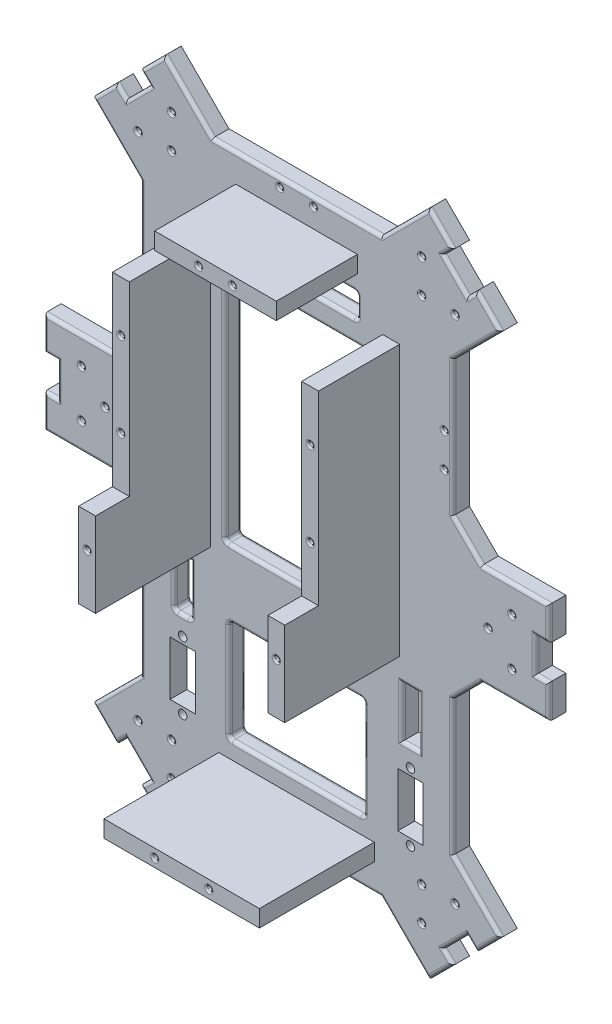
SolidWorks part; units mm, degrees
ref_plane "Płaszczyzna przednia" through (0, 0, 0) normal (0, 0, 1) x (1, 0, 0)
ref_plane "Płaszczyzna górna" through (0, 0, 0) normal (0, 1, 0) x (1, 0, 0)
ref_plane "Płaszczyzna prawa" through (0, 0, 0) normal (1, 0, 0) x (0, 0, -1)
sketch "Szkic1" plane through (0, 0, 0) normal (0, 0, 1) x (1, 0, 0)
  line L0 (0, 0) -> (-50, 0)
  line L1 (-50, 0) -> (-64.1421, 14.1421)
  line L2 (-64.1421, 14.1421) -> (-71.2132, 7.0711)
  line L3 (-71.2132, 7.0711) -> (-68.3848, 4.2426)
  line L4 (-68.3848, 4.2426) -> (-75.4558, -2.8284)
  line L5 (-75.4558, -2.8284) -> (-78.2843, 0)
  line L6 (-78.2843, 0) -> (-85.3553, -7.0711)
  line L7 (-85.3553, -7.0711) -> (-71.2132, -21.2132)
  line L8 (-71.2132, -21.2132) -> (-71.2132, -61.2132)
  line L9 (0, 0) -> (14.1421, 14.1421)
  line L10 (14.1421, 14.1421) -> (21.2132, 7.0711)
  line L11 (21.2132, 7.0711) -> (18.3848, 4.2426)
  line L12 (18.3848, 4.2426) -> (25.4558, -2.8284)
  line L13 (25.4558, -2.8284) -> (28.2843, 0)
  line L14 (28.2843, 0) -> (35.3553, -7.0711)
  line L15 (35.3553, -7.0711) -> (21.2132, -21.2132)
  line L16 (21.2132, -21.2132) -> (21.2132, -61.2132)
  line L17 (-71.2132, -61.2132) -> (-79.6985, -69.6985)
  line L18 (-79.6985, -69.6985) -> (-99.6985, -69.6985)
  line L19 (-99.6985, -69.6985) -> (-99.6985, -79.6985)
  line L20 (-99.6985, -79.6985) -> (-95.6985, -79.6985)
  line L21 (-95.6985, -79.6985) -> (-95.6985, -89.6985)
  line L22 (-95.6985, -89.6985) -> (-99.6985, -89.6985)
  line L23 (-99.6985, -89.6985) -> (-99.6985, -99.6985)
  line L24 (-99.6985, -99.6985) -> (-79.6985, -99.6985)
  line L25 (21.2132, -61.2132) -> (29.6985, -69.6985)
  line L26 (29.6985, -69.6985) -> (49.6985, -69.6985)
  line L27 (49.6985, -69.6985) -> (49.6985, -79.6985)
  line L28 (49.6985, -79.6985) -> (45.6985, -79.6985)
  line L29 (45.6985, -79.6985) -> (45.6985, -89.6985)
  line L30 (45.6985, -89.6985) -> (49.6985, -89.6985)
  line L31 (49.6985, -89.6985) -> (49.6985, -99.6985)
  line L32 (49.6985, -99.6985) -> (29.6985, -99.6985)
  line L33 (29.6985, -99.6985) -> (21.2132, -108.1838)
  line L34 (-79.6985, -99.6985) -> (-71.2132, -108.1838)
  line L35 (-71.2132, -108.1838) -> (-71.2132, -148.1838)
  line L36 (21.2132, -108.1838) -> (21.2132, -148.1838)
  line L37 (-71.2132, -148.1838) -> (-85.3553, -162.3259)
  line L38 (-85.3553, -162.3259) -> (-78.2843, -169.397)
  line L39 (-78.2843, -169.397) -> (-75.4558, -166.5685)
  line L40 (-75.4558, -166.5685) -> (-68.3848, -173.6396)
  line L41 (-68.3848, -173.6396) -> (-71.2132, -176.468)
  line L42 (-71.2132, -176.468) -> (-64.1421, -183.5391)
  line L43 (-64.1421, -183.5391) -> (-50, -169.397)
  line L44 (21.2132, -148.1838) -> (35.3553, -162.3259)
  line L45 (35.3553, -162.3259) -> (28.2843, -169.397)
  line L46 (28.2843, -169.397) -> (25.4558, -166.5685)
  line L47 (25.4558, -166.5685) -> (18.3848, -173.6396)
  line L48 (18.3848, -173.6396) -> (21.2132, -176.468)
  line L49 (21.2132, -176.468) -> (14.1421, -183.5391)
  line L50 (14.1421, -183.5391) -> (0, -169.397)
  line L51 (-50, -169.397) -> (0, -169.397)
  dimension "D1" = 225
  dimension "D2" = 225
  dimension "D3" = 20
  dimension "D4" = 20
  dimension "D5" = 10
  dimension "D6" = 4
  dimension "D7" = 50
  dimension "D8" = 10
  dimension "D9" = 10
  dimension "D10" = 20
  dimension "D11" = 4
  dimension "D12" = 10
  dimension "D13" = 4
  dimension "D14" = 10
  dimension "D15" = 4
  dimension "D16" = 10
  dimension "D17" = 20
  dimension "D18" = 225
  dimension "D19" = 40
  dimension "D20" = 12
  dimension "D21" = 20
  dimension "D22" = 10
  dimension "D23" = 4
  dimension "D24" = 10
  dimension "D25" = 4
  dimension "D26" = 10
  dimension "D27" = 20
  dimension "D29" = 12
  dimension "D30" = 20
  dimension "D31" = 10
  dimension "D32" = 4
  dimension "D33" = 10
  dimension "D34" = 4
  dimension "D35" = 10
  dimension "D36" = 20
  dimension "D37" = 12
  dimension "D38" = 12
  dimension "D39" = 40
  dimension "D40" = 40
  dimension "D41" = 20
  dimension "D42" = 10
  dimension "D43" = 4
  dimension "D44" = 10
  dimension "D45" = 4
  dimension "D46" = 10
  dimension "D47" = 20
  dimension "D48" = 20
  dimension "D49" = 10
  dimension "D50" = 4
  dimension "D51" = 10
  dimension "D52" = 4
  dimension "D53" = 10
  dimension "D54" = 20
  dimension "D55" = 135
  dimension "D56" = 90
  dimension "D57" = 270
  dimension "D58" = 225
  dimension "D59" = 225
  dimension "D60" = 135
extrude "Dodanie-wyciągnięcie1" add sketch "Szkic1" along normal blind 5 contours L36 L44 L45 L46 L47 L48 L49 L50 L51 L43 L42 L41 L40 L39 L38 L37 L35 L34 L24 L23 L22 L21 L20 L19 L18 L17 L8 L7 L6 L5 L4 L3 L2 L1 L0 L9 L10 L11 L12 L13 L14 L15 L16 L25 L26 L27 L28 L29 L30 L31 L32 L33
sketch "Szkic11" plane through (0, 0, 5) normal (0, 0, 1) x (1, 0, 0)
  line L0 (-79.6985, -69.6985) -> (-99.6985, -69.6985) construction
  line L1 (-85.3553, -7.0711) -> (-71.2132, -21.2132) construction
  line L2 (-99.6985, -69.6985) -> (-99.6985, -79.6985) construction
  line L3 (-99.6985, -99.6985) -> (-79.6985, -99.6985) construction
  line L4 (-78.2843, 0) -> (-85.3553, -7.0711) construction
  line L5 (-50, 0) -> (-64.1421, 14.1421) construction
  line L6 (-64.1421, 14.1421) -> (-71.2132, 7.0711) construction
  line L7 (14.1421, 14.1421) -> (21.2132, 7.0711) construction
  line L8 (35.3553, -7.0711) -> (21.2132, -21.2132) construction
  line L9 (28.2843, 0) -> (35.3553, -7.0711) construction
  line L10 (0, 0) -> (14.1421, 14.1421) construction
  line L11 (49.6985, -89.6985) -> (49.6985, -99.6985) construction
  line L12 (49.6985, -99.6985) -> (29.6985, -99.6985) construction
  line L13 (49.6985, -69.6985) -> (49.6985, -79.6985) construction
  line L14 (29.6985, -69.6985) -> (49.6985, -69.6985) construction
  line L15 (21.2132, -176.468) -> (14.1421, -183.5391) construction
  line L16 (14.1421, -183.5391) -> (0, -169.397) construction
  line L17 (35.3553, -162.3259) -> (28.2843, -169.397) construction
  line L18 (21.2132, -148.1838) -> (35.3553, -162.3259) construction
  line L19 (-85.3553, -162.3259) -> (-78.2843, -169.397) construction
  line L20 (-71.2132, -176.468) -> (-64.1421, -183.5391) construction
  line L21 (-64.1421, -183.5391) -> (-50, -169.397) construction
  line L22 (-71.2132, -148.1838) -> (-85.3553, -162.3259) construction
  line L23 (-99.6985, -89.6985) -> (-99.6985, -99.6985) construction
  circle A0 centre (-81.6985, -84.6985) radius 0.8
  circle A1 centre (-88.6985, -77.6985) radius 0.8
  circle A2 centre (-88.6985, -91.6985) radius 0.8
  circle A3 centre (-62.0208, -9.1924) radius 0.8
  circle A4 centre (-62.0208, 0.7071) radius 0.8
  circle A5 centre (-71.9203, -9.1924) radius 0.8
  circle A6 centre (12.0208, -9.1924) radius 0.8
  circle A7 centre (12.0208, 0.7071) radius 0.8
  circle A8 centre (21.9203, -9.1924) radius 0.8
  circle A9 centre (31.6985, -84.6985) radius 0.8
  circle A10 centre (38.6985, -77.6985) radius 0.8
  circle A11 centre (38.6985, -91.6985) radius 0.8
  circle A12 centre (12.0208, -160.2046) radius 0.8
  circle A13 centre (21.9203, -160.2046) radius 0.8
  circle A14 centre (12.0208, -170.1041) radius 0.8
  circle A15 centre (-62.0208, -160.2046) radius 0.8
  circle A16 centre (-71.9203, -160.2046) radius 0.8
  circle A17 centre (-62.0208, -170.1041) radius 0.8
  dimension "D1" = 1.6
  dimension "D4" = 1.6
  dimension "D5" = 1.6
  dimension "D10" = 1.6
  dimension "D11" = 1.6
  dimension "D12" = 1.6
  dimension "D19" = 1.6
  dimension "D20" = 1.6
  dimension "D21" = 1.6
  dimension "D30" = 1.6
  dimension "D31" = 1.6
  dimension "D32" = 1.6
  dimension "D41" = 1.6
  dimension "D42" = 1.6
  dimension "D43" = 1.6
  dimension "D50" = 1.6
  dimension "D51" = 1.6
  dimension "D52" = 1.6
  dimension "D2" = 15
  dimension "D3" = 18
  dimension "D6" = 7
  dimension "D7" = 7
  dimension "D8" = 8
  dimension "D9" = 8
  dimension "D13" = 18
  dimension "D14" = 15
  dimension "D15" = 8
  dimension "D16" = 8
  dimension "D17" = 11
  dimension "D18" = 11
  dimension "D22" = 18
  dimension "D23" = 15
  dimension "D24" = 11
  dimension "D25" = 11
  dimension "D26" = 8
  dimension "D27" = 8
  dimension "D28" = 14
  dimension "D29" = 14
  dimension "D33" = 18
  dimension "D34" = 15
  dimension "D35" = 11
  dimension "D36" = 11
  dimension "D37" = 8
  dimension "D38" = 8
  dimension "D39" = 14
  dimension "D40" = 7
  dimension "D44" = 18
  dimension "D45" = 15
  dimension "D46" = 11
  dimension "D47" = 11
  dimension "D48" = 8
  dimension "D49" = 8
  dimension "D53" = 18
  dimension "D54" = 11
  dimension "D55" = 11
  dimension "D56" = 8
  dimension "D57" = 15
  dimension "D58" = 8
  dimension "D59" = 14
  dimension "D60" = 14
  dimension "D61" = 14
  dimension "D62" = 11
  dimension "D63" = 11
extrude "Wytnij-wyciągnięcie7" cut sketch "Szkic11" against normal blind 60 and the other way blind 42
sketch "Szkic12" plane through (0, 0, 5) normal (0, 0, 1) x (1, 0, 0)
  line L0 (0, 0) -> (-50, 0) construction
  line L1 (-71.2132, -21.2132) -> (-71.2132, -61.2132) construction
  line L2 (-50, -169.397) -> (0, -169.397) construction
  line L3 (21.2132, -21.2132) -> (21.2132, -61.2132) construction
  circle A0 centre (-30, -2.5) radius 0.75
  circle A1 centre (-20, -2.5) radius 0.75
  circle A2 centre (-30, -166.897) radius 0.75
  circle A3 centre (-20, -166.897) radius 0.75
  circle A4 centre (-68.7132, -40.5) radius 0.75
  circle A5 centre (-68.7132, -50.5) radius 0.75
  circle A6 centre (18.7132, -40.5) radius 0.75
  circle A7 centre (18.7132, -50.5) radius 0.75
  dimension "D2" = 1.5
  dimension "D3" = 1.5
  dimension "D8" = 1.5
  dimension "D9" = 1.5
  dimension "D15" = 1.5
  dimension "D16" = 1.5
  dimension "D17" = 1.5
  dimension "D18" = 1.5
  dimension "D1" = 2.5
  dimension "D4" = 2.5
  dimension "D5" = 20
  dimension "D6" = 10
  dimension "D7" = 20
  dimension "D10" = 2.5
  dimension "D11" = 2.5
  dimension "D12" = 20
  dimension "D13" = 10
  dimension "D14" = 20
  dimension "D19" = 2.5
  dimension "D20" = 2.5
  dimension "D21" = 2.5
  dimension "D22" = 2.5
  dimension "D23" = 40.5
  dimension "D24" = 50.5
  dimension "D25" = 40.5
  dimension "D26" = 50.5
extrude "Wytnij-wyciągnięcie8" cut sketch "Szkic12" against normal blind 66 and the other way blind 36
sketch "Szkic13" plane through (0, 0, 0) normal (0, 0, 1) x (1, 0, 0)
  line L0 (0, 0) -> (-50, 0) construction
  line L1 (-46.2132, -31.5) -> (-3.7868, -31.5)
  line L2 (-46.2132, -31.5) -> (-46.2132, -101.5)
  line L3 (-46.2132, -101.5) -> (-3.7868, -101.5)
  line L4 (-3.7868, -31.5) -> (-3.7868, -101.5)
  line L9 (-71.2132, -21.2132) -> (-71.2132, -61.2132) construction
  line L10 (21.2132, -21.2132) -> (21.2132, -61.2132) construction
  line L11 (-71.2132, -108.1838) -> (-71.2132, -148.1838) construction
  line L12 (-45.0032, -121.397) -> (-5.0032, -121.397)
  line L13 (-45.0032, -121.397) -> (-45.0032, -151.397)
  line L14 (-45.0032, -151.397) -> (-5.0032, -151.397)
  line L15 (-5.0032, -121.397) -> (-5.0032, -151.397)
  line L16 (21.2132, -108.1838) -> (21.2132, -148.1838) construction
  line L17 (-50, -169.397) -> (0, -169.397) construction
  line L19 (-61.2132, -111.5) -> (-56.2132, -111.5)
  line L20 (-61.2132, -111.5) -> (-61.2132, -126.5)
  line L21 (-61.2132, -126.5) -> (-56.2132, -126.5)
  line L22 (-56.2132, -111.5) -> (-56.2132, -126.5)
  line L23 (-62.4632, -134) -> (-54.9632, -134)
  line L24 (-62.4632, -134) -> (-62.4632, -150)
  line L25 (-62.4632, -150) -> (-54.9632, -150)
  line L26 (-54.9632, -134) -> (-54.9632, -150)
  line L31 (4.9632, -134) -> (12.4632, -134)
  line L32 (4.9632, -134) -> (4.9632, -150)
  line L33 (4.9632, -150) -> (12.4632, -150)
  line L34 (12.4632, -134) -> (12.4632, -150)
  line L35 (-43.0032, -18) -> (-7.0032, -18)
  line L36 (-43.0032, -18) -> (-43.0032, -25)
  line L37 (-43.0032, -25) -> (-7.0032, -25)
  line L38 (-7.0032, -18) -> (-7.0032, -25)
  line L39 (6.2132, -111.5) -> (11.2132, -111.5)
  line L40 (6.2132, -111.5) -> (6.2132, -126.5)
  line L41 (6.2132, -126.5) -> (11.2132, -126.5)
  line L42 (11.2132, -111.5) -> (11.2132, -126.5)
  circle A0 centre (8.7132, -132) radius 1.25
  circle A1 centre (8.7132, -152) radius 1.25
  circle A2 centre (-58.7132, -132) radius 1.25
  circle A3 centre (-58.7132, -152) radius 1.25
  dimension "D39" = 2.5
  dimension "D40" = 2.5
  dimension "D30" = 2.5
  dimension "D41" = 2.5
  dimension "D1" = 70
  dimension "D2" = 31.5
  dimension "D3" = 25
  dimension "D5" = 25
  dimension "D6" = 15
  dimension "D7" = 12.603
  dimension "D8" = 7.5
  dimension "D9" = 40
  dimension "D10" = 26.21
  dimension "D11" = 26.2164
  dimension "D12" = 30
  dimension "D13" = 18
  dimension "D14" = 2
  dimension "D15" = 10
  dimension "D16" = 5
  dimension "D17" = 10
  dimension "D18" = 15
  dimension "D19" = 8.75
  dimension "D20" = 7.5
  dimension "D21" = 7.5
  dimension "D22" = 16
  dimension "D23" = 0
  dimension "D24" = 7.5
  dimension "D25" = 5
  dimension "D26" = 3.75
  dimension "D27" = 3.75
  dimension "D28" = 8.75
  dimension "D29" = 16
  dimension "D31" = 9.9664
  dimension "D32" = 28.21
  dimension "D33" = 36
  dimension "D34" = 28.2164
  dimension "D35" = 7
  dimension "D36" = 18
  dimension "D37" = 3.75
  dimension "D38" = 3.75
  dimension "50" = 20
  dimension "D42" = 2
  dimension "D43" = 2
  dimension "D44" = 10
extrude "Wytnij-wyciągnięcie9" cut sketch "Szkic13" against normal blind 47 and the other way blind 54
sketch "Szkic14" plane through (0, 0, 5) normal (0, 0, 1) x (1, 0, 0)
  line L0 (-50.4982, -25) -> (-55.4982, -25)
  line L1 (-55.4982, -25) -> (-55.4982, -105)
  line L2 (-55.4982, -105) -> (-50.4982, -105)
  line L3 (-50.4982, -105) -> (-50.4982, -25)
  line L4 (5.5018, -25) -> (5.5018, -105)
  line L5 (5.5018, -105) -> (0.5018, -105)
  line L6 (0.5018, -25) -> (5.5018, -25)
  line L7 (0.5018, -105) -> (0.5018, -25)
  line L8 (-46.2132, -101.5) -> (-46.2132, -31.5) construction
  line L10 (-5.0032, -151.397) -> (-45.0032, -151.397) construction
  line L11 (0, 0) -> (-50, 0) construction
  line L12 (-3.7868, -31.5) -> (-3.7868, -101.5) construction
  line L13 (-48.0032, -156.397) -> (-2.0032, -156.397)
  line L14 (-2.0032, -156.397) -> (-2.0032, -161.397)
  line L15 (-2.0032, -161.397) -> (-48.0032, -161.397)
  line L16 (-48.0032, -161.397) -> (-48.0032, -156.397)
  line L18 (-71.2132, -108.1838) -> (-71.2132, -148.1838) construction
  line L19 (-43.0032, -13.197) -> (-7.0032, -13.197)
  line L20 (-7.0032, -13.197) -> (-7.0032, -8.197)
  line L21 (-7.0032, -8.197) -> (-43.0032, -8.197)
  line L22 (-43.0032, -8.197) -> (-43.0032, -13.197)
  line L24 (-71.2132, -21.2132) -> (-71.2132, -61.2132) construction
  circle A0 centre (-30.0032, -10.697) radius 0.75
  circle A1 centre (-20.0032, -10.697) radius 0.75
  circle A2 centre (-33.0032, -158.897) radius 0.75
  circle A3 centre (-17.0032, -158.897) radius 0.75
  circle A4 centre (-52.9982, -40) radius 0.75
  circle A5 centre (-52.9982, -65) radius 0.75
  circle A6 centre (-52.9982, -90) radius 0.75
  circle A7 centre (3.0018, -40) radius 0.75
  circle A8 centre (3.0018, -65) radius 0.75
  circle A9 centre (3.0018, -90) radius 0.75
  dimension "D21" = 1.5
  dimension "D22" = 1.5
  dimension "D26" = 1.5
  dimension "D27" = 1.5
  dimension "D33" = 1.5
  dimension "D34" = 1.5
  dimension "D35" = 1.5
  dimension "D42" = 1.5
  dimension "D43" = 1.5
  dimension "D44" = 1.5
  dimension "D1" = 80
  dimension "D2" = 5
  dimension "D3" = 5
  dimension "D4" = 80
  dimension "D5" = 51
  dimension "D6" = 4.285
  dimension "D7" = 4.2886
  dimension "D8" = 25
  dimension "D9" = 25
  dimension "D10" = 5
  dimension "D11" = 5
  dimension "D12" = 46
  dimension "D13" = 23.21
  dimension "D14" = 143.2
  dimension "D15" = 5
  dimension "D16" = 28.21
  dimension "D17" = 36
  dimension "D18" = 2.5
  dimension "D19" = 2.5
  dimension "D20" = 10
  dimension "D23" = 13
  dimension "D24" = 2.5
  dimension "D25" = 2.5
  dimension "D28" = 16
  dimension "D29" = 15
  dimension "D30" = 2.5
  dimension "D31" = 2.5
  dimension "D32" = 2.5
  dimension "D36" = 25
  dimension "D37" = 25
  dimension "D38" = 15
  dimension "D39" = 2.5
  dimension "D40" = 2.5
  dimension "D41" = 2.5
  dimension "D45" = 15
  dimension "D46" = 25
  dimension "D47" = 25
extrude "Dodanie-wyciągnięcie7" add sketch "Szkic14" along normal blind 24
extrude "Dodanie-wyciągnięcie8" add sketch "Szkic14<9>" along normal blind 34 contours L16 L15 L14 L13 A3 A2 region at (-25.0032, -158.897, 5)
sketch "Szkic14<9>" plane through (0, 0, 5) normal (0, 0, 1) x (1, 0, 0) same geometry as "Szkic14"
sketch "Szkic17" plane through (0, 0, 0) normal (0, 0, 1) x (1, 0, 0)
  line L0 (-50.4982, -80) -> (-55.4982, -80)
  line L1 (-50.4982, -105) -> (-50.4982, -25) construction
  line L2 (-55.4982, -25) -> (-55.4982, -105) construction
  line L3 (-55.4982, -80) -> (-55.4982, -105)
  line L4 (-55.4982, -105) -> (-50.4982, -105)
  line L5 (-50.4982, -105) -> (-50.4982, -80)
  line L6 (0.5018, -105) -> (5.5018, -105)
  line L7 (5.5018, -105) -> (5.5018, -80)
  line L8 (5.5018, -105) -> (5.5018, -25) construction
  line L9 (5.5018, -80) -> (0.5018, -80)
  line L10 (0.5018, -25) -> (0.5018, -105) construction
  line L11 (0.5018, -80) -> (0.5018, -105)
  circle A0 centre (-52.9982, -90) radius 0.75
  circle A1 centre (3.0018, -90) radius 0.75
  dimension "D3" = 1.5
  dimension "D4" = 1.5
  dimension "D1" = 25
  dimension "D2" = 25
extrude "Dodanie-wyciągnięcie9" add sketch "Szkic17" along normal blind 39
fillet "Zaokrąglenie3" radius 1 52 edges at (-97.6985, -79.6985, 5) (-95.6985, -84.6985, 5) (-97.6985, -89.6985, 5) (-99.6985, -94.6985, 5) (-89.6985, -99.6985, 5) (-75.4558, -103.9411, 5) (-71.2132, -128.1838, 5) (-78.2843, -155.2548, 5) (-76.8701, -167.9828, 5) (-69.799, -175.0538, 5) (-81.8198, -165.8614, 5) (-71.9203, -170.1041, 5) (-67.6777, -180.0036, 5) (-57.0711, -176.468, 5) (-25, -169.397, 5) (7.0711, -176.468, 5) (17.6777, -180.0036, 5) (19.799, -175.0538, 5) (21.9203, -170.1041, 5) (26.8701, -167.9828, 5) (31.8198, -165.8614, 5) (28.2843, -155.2548, 5) (21.2132, -128.1838, 5) (25.4558, -103.9411, 5) (39.6985, -99.6985, 5) (49.6985, -94.6985, 5) (47.6985, -89.6985, 5) (45.6985, -84.6985, 5) (47.6985, -79.6985, 5) (49.6985, -74.6985, 5) (39.6985, -69.6985, 5) (25.4558, -65.4558, 5) (21.2132, -41.2132, 5) (28.2843, -14.1421, 5) (31.8198, -3.5355, 5) (26.8701, -1.4142, 5) (21.9203, 0.7071, 5) (19.799, 5.6569, 5) (17.6777, 10.6066, 5) (7.0711, 7.0711, 5) (-25, 0, 5) (-69.799, 5.6569, 5) (-67.6777, 10.6066, 5) (-57.0711, 7.0711, 5) (-71.9203, 0.7071, 5) (-76.8701, -1.4142, 5) (-81.8198, -3.5355, 5) (-78.2843, -14.1421, 5) (-71.2132, -41.2132, 5) (-75.4558, -65.4558, 5) (-89.6985, -69.6985, 5) (-99.6985, -74.6985, 5)
fillet "Zaokrąglenie4" radius 1 50 edges at (-56.2132, -119, 5) (-61.2132, -119, 5) (-61.2132, -119, 0) (-56.2132, -119, 0) (-45.0032, -136.397, 5) (-5.0032, -136.397, 5) (-5.0032, -136.397, 0) (-45.0032, -136.397, 0) (-46.2132, -66.5, 5) (-3.7868, -66.5, 5) (-3.7868, -66.5, 0) (-46.2132, -66.5, 0) (-7.0032, -21.5, 5) (-43.0032, -21.5, 5) (-43.0032, -21.5, 0) (-7.0032, -21.5, 0) (-58.7132, -126.5, 5) (-61.2132, -126.5, 2.5) (-58.7132, -126.5, 0) (-56.2132, -126.5, 2.5) (-25.0032, -151.397, 5) (-45.0032, -151.397, 2.5) (-25.0032, -151.397, 0) (-5.0032, -151.397, 2.5) (-25.0032, -121.397, 5) (-5.0032, -121.397, 2.5) (-25.0032, -121.397, 0) (-45.0032, -121.397, 2.5) (-25, -101.5, 5) (-46.2132, -101.5, 2.5) (-25, -101.5, 0) (-3.7868, -101.5, 2.5) (-25, -31.5, 5) (-3.7868, -31.5, 2.5) (-25, -31.5, 0) (-46.2132, -31.5, 2.5) (-25.0032, -18, 5) (-7.0032, -18, 2.5) (-25.0032, -18, 0) (-43.0032, -18, 2.5) (-25.0032, -25, 5) (-43.0032, -25, 2.5) (-25.0032, -25, 0) (-7.0032, -25, 2.5) (-58.7132, -111.5, 0) (-58.7132, -111.5, 5) (8.7132, -126.5, 5) (11.2132, -119, 5) (8.7132, -111.5, 5) (6.2132, -119, 5)
fillet "Zaokrąglenie5" radius 0.5 36 edges at (12.8208, -170.1041, 5) (12.8208, -160.2046, 5) (22.7203, -160.2046, 5) (-19.25, -166.897, 5) (-29.25, -166.897, 5) (-61.2208, -170.1041, 5) (-61.2208, -160.2046, 5) (-71.1203, -160.2046, 5) (-67.9632, -50.5, 5) (-67.9632, -40.5, 5) (39.4985, -91.6985, 5) (32.4985, -84.6985, 5) (39.4985, -77.6985, 5) (19.4632, -50.5, 5) (19.4632, -40.5, 5) (22.7203, -9.1924, 5) (12.8208, -9.1924, 5) (-29.25, -2.5, 5) (-19.25, -2.5, 5) (12.8208, 0.7071, 5) (-61.2208, -9.1924, 5) (-71.1203, -9.1924, 5) (-61.2208, 0.7071, 5) (-87.8985, -91.6985, 5) (-80.8985, -84.6985, 5) (-87.8985, -77.6985, 5) (-19.2532, -10.697, 29) (-29.2532, -10.697, 29) (-32.2532, -158.897, 39) (-16.2532, -158.897, 39) (3.7518, -90, 39) (3.7518, -65, 29) (3.7518, -40, 29) (-52.2482, -90, 39) (-52.2482, -65, 29) (-52.2482, -40, 29)
